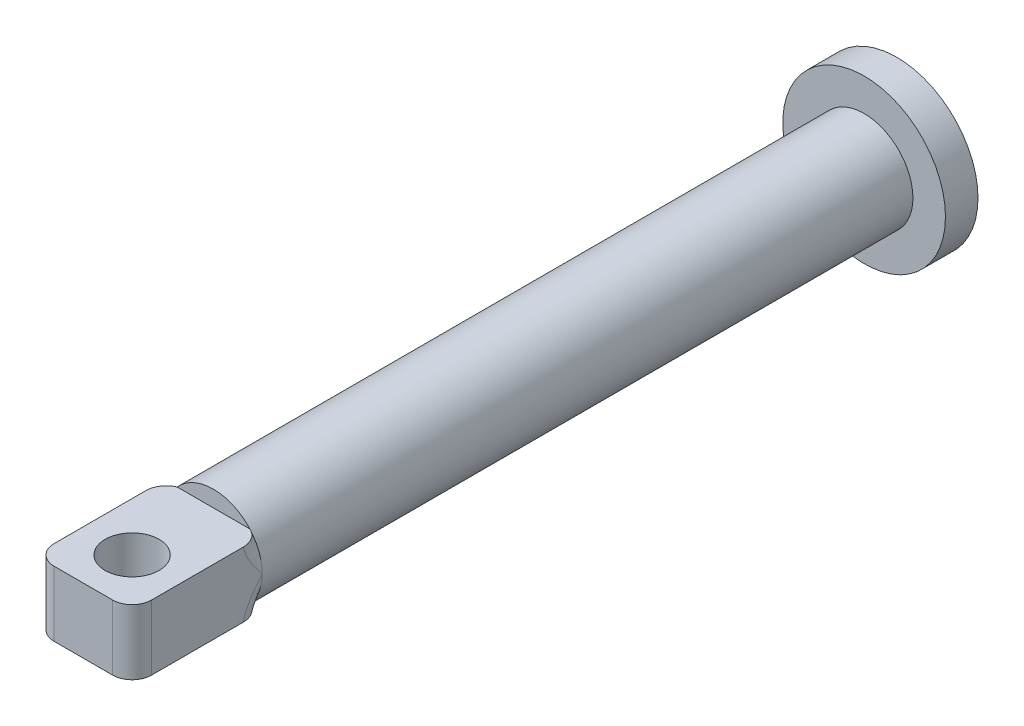
SolidWorks part; units mm, degrees
ref_plane "Front Plane" through (0, 0, 0) normal (0, 0, 1) x (1, 0, 0)
ref_plane "Top Plane" through (0, 0, 0) normal (0, 1, 0) x (1, 0, 0)
ref_plane "Right Plane" through (0, 0, 0) normal (1, 0, 0) x (0, 0, -1)
sketch "Sketch1" plane through (0, 0, 0) normal (0, 0, 1) x (1, 0, 0)
  circle A0 centre (0, 0) radius 12.5
  dimension "D1" = 25
extrude "Boss-Extrude1" add sketch "Sketch1" along normal blind 5 contours A0
sketch "Sketch2" plane through (0, 0, 5) normal (0, 0, 1) x (1, 0, 0)
  circle A0 centre (0, 0) radius 7.5
  dimension "D1" = 15
extrude "Boss-Extrude2" add sketch "Sketch2" along normal blind 100
sketch "Sketch3" plane through (0, 0, 0) normal (0, 1, 0) x (1, 0, 0)
  line L0 (0, -105) -> (0, -125) construction
  line L1 (-7.5, -105) -> (7.5, -105) construction
  line L3 (-7.5, -105) -> (7.5, -105)
  line L4 (-7.5, -105) -> (-7.5, -125)
  line L5 (-7.5, -125) -> (7.5, -125)
  line L6 (7.5, -105) -> (7.5, -125)
  line L7 (-7.5, -105) -> (7.5, -125) construction
  line L8 (-7.5, -125) -> (7.5, -105) construction
  circle A0 centre (0, -117.5) radius 4.15
  point P5 (0, -115)
  dimension "D3" = 8.3
  dimension "D1" = 20
  dimension "D2" = 15
  dimension "D4" = 7.5
extrude "Boss-Extrude3" add sketch "Sketch3" along normal blind 5 and the other way blind 5
fillet "Fillet1" radius 3 6 edges at (-7.5, 0, 125) (7.5, 0, 125) (-7.5, -2.5, 105) (7.5, 2.5, 105) (-7.5, 2.5, 105) (7.5, -2.5, 105)
